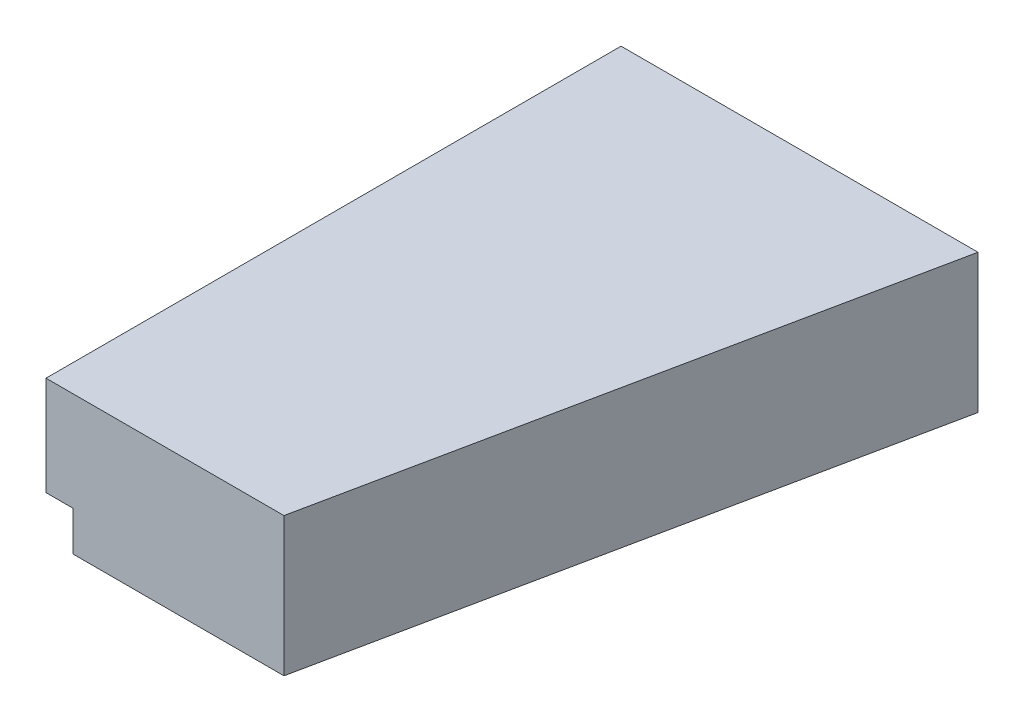
SolidWorks part; units mm, degrees
ref_plane "Front Plane" through (0, 0, 0) normal (1, 0, 0) x (0, 1, 0)
ref_plane "Top Plane" through (0, 0, 0) normal (0, 0, 1) x (0, 1, 0)
ref_plane "Right Plane" through (0, 0, 0) normal (0, 1, 0) x (-1, 0, 0)
sketch "Sketch1" plane through (0, 0, 0) normal (0, 1, 0) x (-1, 0, 0)
  line L0 (-13.4363, 2.5951) -> (16.5637, 147.5951)
  line L1 (-13.4363, -4.9049) -> (-8.4363, -4.9049)
  line L2 (-13.4363, -4.9049) -> (-13.4363, 2.5951)
  line L3 (-13.4363, 2.5951) -> (-8.4363, 2.5951)
  line L4 (-8.4363, -4.9049) -> (-8.4363, 2.5951)
  line L13 (-13.4363, 2.5951) -> (16.5637, 147.5951)
  line L14 (-13.4363, 2.5951) -> (-3.6437, 0.569)
  line L15 (-13.4363, 2.5951) -> (66.5637, 2.5951) construction
  line L16 (-13.4363, 2.5951) -> (-13.4363, 137.5951) construction
  line L17 (-13.4363, 137.5951) -> (66.5637, 137.5951) construction
  line L18 (66.5637, 2.5951) -> (66.5637, 137.5951) construction
  line L19 (66.5637, 137.5951) -> (16.5637, 137.5951)
  line L20 (66.5637, 137.5951) -> (66.5637, 147.5951)
  line L21 (66.5637, 147.5951) -> (16.5637, 147.5951)
  line L22 (16.5637, 137.5951) -> (16.5637, 147.5951)
  line L23 (16.5637, 147.5951) -> (26.3563, 145.569)
  line L24 (-3.6437, 0.569) -> (26.3563, 145.569)
  line L25 (-8.4363, 2.5951) -> (-3.2246, 2.5951)
  line L27 (-3.2246, 2.5951) -> (66.5637, 2.5951)
  line L28 (-3.2246, 2.5951) -> (-3.2246, 7.5951)
  line L29 (-3.2246, 7.5951) -> (66.5637, 7.5951)
  line L30 (66.5637, 2.5951) -> (66.5637, 7.5951)
  line L35 (66.5637, 147.5951) -> (76.5637, 147.5951)
  line L36 (66.5637, 147.5951) -> (66.5637, 2.5951)
  line L37 (66.5637, 2.5951) -> (76.5637, 2.5951)
  line L38 (76.5637, 147.5951) -> (76.5637, 2.5951)
  dimension "D1" = 7.5
  dimension "D3" = 135
  dimension "D4" = 80
  dimension "D5" = 10
  dimension "D7" = 10
  dimension "D9" = 5
  dimension "D8" = 10
  dimension "D6" = 50
extrude "Boss-Extrude1" add sketch "Sketch1" along normal blind 35 contours L24 L19 L20 L21 L23 | L19 L24 L23 L22 | L3 L25 L24 L19 L22 L0 | L29 L28 L24 | L27 L30 L29 L24 | L38 L35 L20 L36 L30 L37 region at (-5.7274, 0, 70.7433) region at (-20.91, 0, 142.2574) region at (-45.5816, 0, 142.6608) region at (-71.5637, 0, 75.0951) region at (2.8797, 0, 5.9284) region at (-31.9275, 0, 5.0889)
sketch "Sketch2" plane through (0, 35, 0) normal (0, 1, 0) x (-1, 0, 0)
  line L0 (16.5637, 147.5951) -> (76.5637, 147.5951)
  line L1 (76.5637, 147.5951) -> (76.5637, 2.5951)
  line L2 (76.5637, 2.5951) -> (-13.4363, 2.5951)
  line L3 (-13.4363, 2.5951) -> (16.5637, 147.5951)
  line L5 (-13.4363, 2.5951) -> (76.5637, 2.5951) construction
extrude "Boss-Extrude2" add sketch "Sketch2" against normal blind 10
sketch "Sketch3" plane through (0, 0, 0) normal (0, -1, 0) x (1, 0, 0)
  line L1 (-24.7065, 147.5951) -> (-66.5637, 147.5951)
  line L2 (-24.7065, 147.5951) -> (-24.7065, 137.5951)
  line L3 (-24.7065, 137.5951) -> (-66.5637, 137.5951)
  line L4 (-66.5637, 147.5951) -> (-66.5637, 137.5951)
  line L17 (-76.5637, 147.5951) -> (-16.5637, 147.5951) construction
  line L22 (2.1901, 7.5951) -> (-24.7065, 137.5951)
  line L23 (2.1901, 7.5951) -> (11.9827, 9.6211)
  line L24 (-24.7065, 137.5951) -> (-14.9139, 139.6211)
  line L26 (11.9827, 9.6211) -> (-14.9139, 139.6211)
  line L27 (13.4363, 2.5951) -> (-16.5637, 147.5951) construction
  line L28 (-27.9565, 140.8451) -> (-63.3137, 140.8451)
  line L29 (-63.3137, 144.3451) -> (-63.3137, 140.8451)
  line L30 (-27.9565, 144.3451) -> (-63.3137, 144.3451)
  line L31 (-27.9565, 144.3451) -> (-27.9565, 140.8451)
  line L32 (-20.8654, 135.071) -> (-17.438, 135.7801)
  line L33 (8.1416, 12.1453) -> (-17.438, 135.7801)
  line L34 (4.7142, 11.4361) -> (8.1416, 12.1453)
  line L35 (4.7142, 11.4361) -> (-20.8654, 135.071)
  line L36 (-17.438, 135.7801) -> (-20.8654, 135.071)
  line L37 (-20.8654, 135.071) -> (-23.4566, 147.5951)
  line L38 (-17.438, 135.7801) -> (-19.8825, 147.5951)
  line L39 (-27.9565, 140.8451) -> (-18.4859, 140.8451)
  line L40 (-27.9565, 144.3451) -> (-19.2101, 144.3451)
  line L41 (-19.2101, 144.3451) -> (-18.4859, 140.8451)
  dimension "D1" = 3.25
extrude "Cut-Extrude1" cut sketch "Sketch3" against normal blind 10 contours L31 L30 L29 L28 | L35 L34 L33 L32 region at (-45.6351, 0, 142.5951) region at (-6.3619, 0, 73.6081)
sketch "Sketch4" plane through (0, 0, 22.5951) normal (0, 1, 0) x (1, 0, 0)
  line L5 (13.4363, 20) -> (-76.5637, 20) construction
  line L6 (-66.5637, 15) -> (2.1901, 15)
  line L7 (-66.5637, 15) -> (-66.5637, 20)
  line L8 (-66.5637, 20) -> (2.1901, 20)
  line L9 (2.1901, 15) -> (2.1901, 20)
  line L10 (2.1901, 15) -> (3.2246, 20)
  line L11 (2.1901, 15) -> (-24.7065, -115) construction
  line L12 (3.2246, 20) -> (2.1901, 20)
  line M13 (2.1901, 15) -> (-66.5637, 15)
  line M20 (-76.5637, 20) -> (13.4363, 20)
extrude "Cut-Extrude2" cut sketch "Sketch4" along normal blind 0.625 contours L9 L7 M13 M20 | L10 L9 M20 region at (-32.1868, 0, 5.0951) region at (2.5349, 0, 4.2617)
sketch "Sketch5" plane through (0, 0, 7.5951) normal (0, 0, 1) x (1, 0, 0)
  line L1 (-66.5637, 0.625) -> (-59.3137, 0.625) construction
  line L2 (-66.5637, 0.625) -> (-66.5637, 5.625) construction
  line L3 (-66.5637, 5.625) -> (-59.3137, 5.625) construction
  line L4 (-59.3137, 0.625) -> (-59.3137, 5.625) construction
  circle A0 centre (-59.3137, 5.625) radius 1.9
  dimension "D3" = 3.8
  dimension "D1" = 5
  dimension "D2" = 7.25
extrude "Cut-Extrude3" cut sketch "Sketch5" against normal up to next contours A0
sketch "Sketch6" plane through (0, 0, 7.5951) normal (0, 0, 1) x (1, 0, 0)
  circle A0 centre (-59.3137, 5.625) radius 3.35
  dimension "D1" = 6.7
extrude "Cut-Extrude4" cut sketch "Sketch6" against normal blind 2.5
pattern_linear "LPattern1" count 2 spacing 52.5 along (1, 0, 0) of "Cut-Extrude4", "Cut-Extrude3"
sketch "Sketch7" plane through (0, 0, 0) normal (0, -1, 0) x (1, 0, 0)
  line L0 (-66.5637, 2.5951) -> (-76.5637, 2.5951) construction
  line L1 (-76.5637, 147.5951) -> (-73.3137, 147.5951)
  line L2 (-76.5637, 147.5951) -> (-76.5637, 2.5951)
  line L3 (-76.5637, 2.5951) -> (-73.3137, 2.5951)
  line L4 (-73.3137, 147.5951) -> (-73.3137, 2.5951) construction
  line L5 (-76.5637, 147.5951) -> (-16.5637, 147.5951) construction
  line L6 (-66.5637, 2.5951) -> (-69.8137, 2.5951)
  line L7 (-66.5637, 2.5951) -> (-66.5637, 147.5951)
  line L8 (-66.5637, 147.5951) -> (-69.8137, 147.5951)
  line L9 (-69.8137, 2.5951) -> (-69.8137, 147.5951) construction
  line L11 (-69.8137, 2.5951) -> (-73.3137, 2.5951)
  line L12 (-69.8137, 2.5951) -> (-69.8137, 147.5951)
  line L13 (-69.8137, 147.5951) -> (-73.3137, 147.5951)
  line L14 (-73.3137, 2.5951) -> (-73.3137, 147.5951)
  line M13 (-76.5637, 2.5951) -> (-66.5637, 2.5951)
  line M20 (-16.5637, 147.5951) -> (-76.5637, 147.5951)
  line M21 (-76.5637, 147.5951) -> (-76.5637, 2.5951)
  dimension "D1" = 3.25
  dimension "D2" = 3.25
extrude "Cut-Extrude5" cut sketch "Sketch7" against normal blind 10 contours L14 L12 M13 M20 | L14 M13 M20 M21 region at (-74.9387, 0, 75.0951) region at (-71.5637, 0, 75.0951)
sketch "Sketch9" plane through (0, 25, 0) normal (0, -1, 0) x (1, 0, 0)
  line L0 (-26.5637, 62.5951) -> (-15.1843, 7.5951)
  line L1 (-66.5637, 7.5951) -> (-26.5637, 7.5951)
  line L2 (-66.5637, 7.5951) -> (-66.5637, 62.5951)
  line L3 (-66.5637, 62.5951) -> (-26.5637, 62.5951)
  line L4 (-26.5637, 7.5951) -> (-26.5637, 62.5951)
  line L5 (-66.5637, 7.5951) -> (2.1901, 7.5951) construction
  line L6 (-26.5637, 7.5951) -> (-15.1843, 7.5951)
  line L7 (-24.7065, 137.5951) -> (2.1901, 7.5951) construction
  line M6 (-66.5637, 137.5951) -> (-66.5637, 7.5951)
  line M7 (-66.5637, 7.5951) -> (2.1901, 7.5951)
  dimension "D1" = 40
  dimension "D2" = 55
extrude "Cut-Extrude6" cut sketch "Sketch9" against normal blind 5 contours L4 L3 M7 M6 | L4 L0 M7 region at (-46.5637, 25, 35.0951) region at (-22.7706, 25, 25.9284)
sketch "Sketch8" plane through (-76.5637, 0, 0) normal (-1, 0, 0) x (0, -1, 0)
  line L1 (-35, 2.5951) -> (-29, 2.5951) construction
  line L2 (-35, 2.5951) -> (-35, 17.5951) construction
  line L3 (-35, 17.5951) -> (-29, 17.5951) construction
  line L4 (-29, 2.5951) -> (-29, 17.5951) construction
  line L5 (-29, 17.5951) -> (-16, 17.5951)
  line L6 (-29, 17.5951) -> (-29, 46.0951)
  line L7 (-29, 46.0951) -> (-16, 46.0951)
  line L8 (-16, 17.5951) -> (-16, 46.0951)
  dimension "D3" = 28.5
  dimension "D4" = 13
extrude "Cut-Extrude7" cut sketch "Sketch8" against normal up to next
sketch "Sketch11" plane through (-66.5637, 0, 0) normal (1, 0, 0) x (0, 1, 0)
  line L0 (14, 48.0951) -> (14, 15.5951)
  line L1 (16, 46.0951) -> (29, 46.0951)
  line L2 (16, 46.0951) -> (16, 17.5951)
  line L3 (16, 17.5951) -> (29, 17.5951)
  line L4 (29, 46.0951) -> (29, 17.5951)
  line L5 (14, 15.5951) -> (31, 15.5951)
  line L6 (31, 48.0951) -> (31, 15.5951)
  line L7 (14, 48.0951) -> (31, 48.0951)
  dimension "D1" = 2
extrude "Cut-Extrude8" cut sketch "Sketch11" against normal blind 7.5
chamfer "Chamfer1" distance 1 distance2 5 1 edges at (-66.5637, 30, 31.8451) first distance on face at (-66.5637, 30.5, 31.8451)
sketch "Sketch12" plane through (-66.5637, 0, 0) normal (1, 0, 0) x (0, 1, 0)
  line L0 (0, 2.5951) -> (0, 147.5951) construction
  line L1 (0, 137.5951) -> (25, 137.5951)
  line L2 (0, 137.5951) -> (0, 123.0951)
  line L3 (0, 123.0951) -> (25, 123.0951)
  line L4 (25, 137.5951) -> (25, 123.0951)
  line L5 (25, 137.5951) -> (0, 137.5951) construction
  line L6 (25, 137.5951) -> (25, 62.5951) construction
  dimension "D1" = 14.5
extrude "Boss-Extrude3" add sketch "Sketch12" along normal blind 2.5
sketch "Sketch13" plane through (-69.8137, 0, 0) normal (-1, 0, 0) x (0, -1, 0)
  line L1 (-10, 147.5951) -> (-5, 147.5951) construction
  line L2 (-10, 147.5951) -> (-10, 130.3451) construction
  line L3 (-10, 130.3451) -> (-5, 130.3451) construction
  line L4 (-5, 147.5951) -> (-5, 130.3451) construction
  circle A0 centre (-5, 130.3451) radius 2.4
  dimension "D3" = 4.8
  dimension "D1" = 17.25
extrude "Cut-Extrude9" cut sketch "Sketch13" against normal blind 3.8
equation "\"whitekey_cutout_length\"= 101.5"
equation "\"key_mount_recess_length\"=50"
equation "\"key_mount_recess_height\"=12.5"
equation "\"key_mount_recess_depth\"=1.5"
equation "\"wall_thickness\"=10"
equation "\"guide_brace_height\"=20"
equation "\"guide_brace_thickness\"=2"
equation "\"dowel_recess_depth\"=10"
equation "\"dowel_recess_offset\"=3.25"
equation "\"dowel_insert_tolerance\"=0.1"
equation "\"base_mount_height\"=40"
equation "\"base_rear_length\"=80"
equation "\"base_front_length\"=111.5"
equation "\"screw_hole_wall_offset\"=7.25"
equation "\"screw_hole_edge_inset\"=\"dowel_recess_depth\"/2"
equation "\"screw_hole_diameter\"=3.8"
equation "\"screw_head_hole_diameter\"=6.7"
equation "\"screw_nut_hole_side_len\"=3.5"
equation "\"screw_nut_recess_offset\"=0.35"
equation "\"screw_head_and_nut_recess_depth\"=2.5"
equation "\"screw_shaft_diameter\"=3.5"
equation "\"switch_board_width\"=30"
equation "\"switch_board_thickness\"=1.6"
equation "\"switch_board_wall_offset\"=11.5"
equation "\"heatset_insert_hole_diameter\"=4.8"
equation "\"heatset_insert_hole_depth\"=3.8"
equation "\"front_rear_panel_width\"=23.75"
equation "\"front_panel_height\"=24"
equation "\"front_rear_panel_recess_depth\"=5"
equation "\"rod_diameter\"=5"
equation "\"rod_head_diameter\"=8"
equation "\"rod_length_adj\"=0.5"
equation "\"rod_insert_length\"=2.8"
equation "\"switch_black_key_mount_height\"=8"
equation "\"switch_white_key_mount_height\"=3"
equation "\"D5@Sketch1\"=\"wall_thickness\""
equation "\"D7@Sketch1\"=\"wall_thickness\""
equation "\"D2@Sketch1\"=\"wall_thickness\"/2"
equation "\"D4@Sketch1\"=\"base_rear_length\""
equation "\"D3@Sketch1\"=\"interface_panel_height\""
equation "\"D1@Sketch1\"=\"wall_thickness\"*0.75"
equation "\"whitekey_spacing\"=1.25"
equation "\"D1@Boss-Extrude1\"=\"side_panel_depth\""
equation "\"D9@Sketch1\"=\"wall_thickness\"/2"
equation "\"D1@Boss-Extrude2\"=\"wall_thickness\""
equation "\"D8@Sketch1\"=\"wall_thickness\""
equation "\"D1@Sketch3\"=\"dowel_recess_offset\""
equation "\"D1@Cut-Extrude1\"=\"dowel_recess_depth\""
equation "\"side_panel_depth\"=35"
equation "\"D1@Sketch5\"=\"screw_hole_edge_inset\""
equation "\"D2@Sketch5\"=\"screw_hole_wall_offset\""
equation "\"D3@Sketch5\"=\"screw_hole_diameter\""
equation "\"D1@Sketch6\"=\"screw_head_hole_diameter\""
equation "\"D1@Cut-Extrude4\"=\"screw_head_and_nut_recess_depth\""
equation "\"D3@LPattern1\"=\"base_rear_length\"-\"screw_hole_wall_offset\"*2-\"wall_thickness\"-3"
equation "\"D1@Sketch7\"=\"dowel_recess_offset\""
equation "\"D2@Sketch7\"=\"dowel_recess_offset\""
equation "\"D1@Cut-Extrude5\"=\"front_rear_panel_recess_depth\"*2"
equation "\"D1@Cut-Extrude2\"=\"whitekey_spacing\"/2"
equation "\"interface_panel_height\"=135"
equation "\"interface_panel_roof_length\"=50"
equation "\"D6@Sketch1\"=\"interface_panel_roof_length\""
equation "\"D1@Sketch8\"=\"wall_thickness\"*1.5"
equation "\"D2@Sketch8\"=\"wall_thickness\"*0.6"
equation "\"D1@Cut-Extrude6\"=\"wall_thickness\"/2"
equation "\"D2@Sketch9\"=\"interface_panel_height\"/3+\"wall_thickness\""
equation "\"D1@Sketch9\"=\"base_rear_length\"/2"
equation "\"D1@Cut-Extrude8\"=\"wall_thickness\"*0.75"
equation "\"D1@Sketch12\"=\"screw_hole_wall_offset\"*2"
equation "\"D1@Boss-Extrude3\"=\"wall_thickness\"/4"
equation "\"D1@Sketch13\"=\"wall_thickness\"+\"screw_hole_wall_offset\""
equation "\"D2@Sketch13\"=\"screw_hole_edge_inset\""
equation "\"D3@Sketch13\"=\"heatset_insert_hole_diameter\""
equation "\"D1@Cut-Extrude9\"=\"heatset_insert_hole_depth\""
